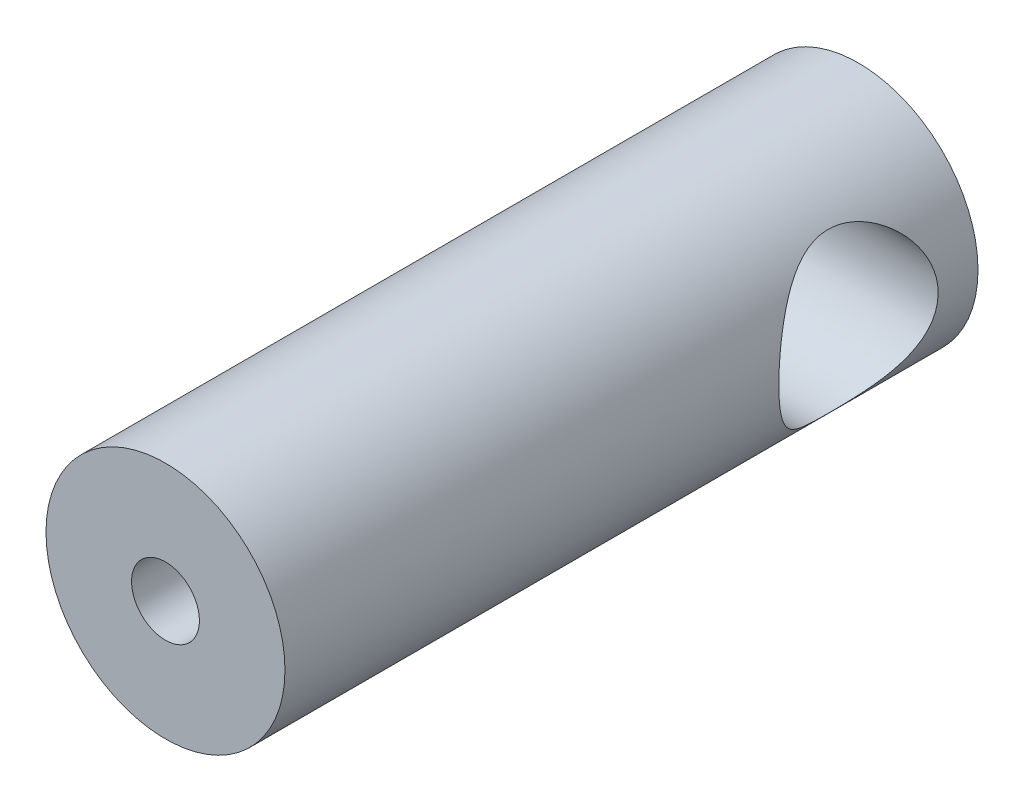
SolidWorks part; units mm, degrees
ref_plane "Front Plane" through (0, 0, 0) normal (0, 0, 1) x (1, 0, 0)
ref_plane "Top Plane" through (0, 0, 0) normal (0, 1, 0) x (1, 0, 0)
ref_plane "Right Plane" through (0, 0, 0) normal (1, 0, 0) x (0, 0, -1)
sketch "Sketch1" plane through (0, 0, 0) normal (0, 0, 1) x (1, 0, 0)
  circle A0 centre (0, 0) radius 4.7625
  dimension "D1" = 9.525
extrude "Boss-Extrude1" add sketch "Sketch1" along normal blind 27.6225
sketch "Sketch2" plane through (0, 0, 27.6225) normal (0, 0, 1) x (1, 0, 0)
  circle A0 centre (0, 0) radius 1.905
  dimension "D1" = 3.81
extrude "Cut-Extrude1" [suppressed] cut sketch "Sketch2" against normal blind 12.7
sketch "Sketch3" plane through (0, 0, 0) normal (1, 0, 0) x (0, 0, -1)
  line L0 (-27.6225, 4.7625) -> (-27.6225, -4.7625) construction
  circle A0 centre (-4.7625, 0) radius 3.175
  dimension "D2" = 6.35
  dimension "D1" = 22.86
extrude "Cut-Extrude2" cut sketch "Sketch3" against normal through all and the other way through all
hole_wizard "#6-32 Tapped Hole1" positions "Sketch5" profile "Sketch6" tap size "#6-32" standard "ANSI Inch"
sketch "Sketch5" plane through (0, 0, 27.6225) normal (0, 0, 1) x (1, 0, 0)
  point P0 (0, 0)
sketch "Sketch6" plane through (0, 0, 27.6225) normal (1, 0, 0) x (0, -1, 0)
  line L0 (0, 0) -> (0, 13.5127)
  line L1 (0, 13.5127) -> (1.3525, 12.7)
  line L2 (1.3525, 12.7) -> (1.3525, 0)
  line L5 (1.3525, 0) -> (0, 0)
  line L10 (0, 13.5127) -> (-1.3526, 12.7) construction
  line L11 (0, -6.35) -> (0, 107.95) construction
  dimension "Tap Drill Dia." = 2.7051
  dimension "Tap Drill Depth" = 12.7
  dimension "Drill Angle" = 118
cosmetic thread "Hole Thread1" parameters "D1"=1.0644, "D2"=3.5052
